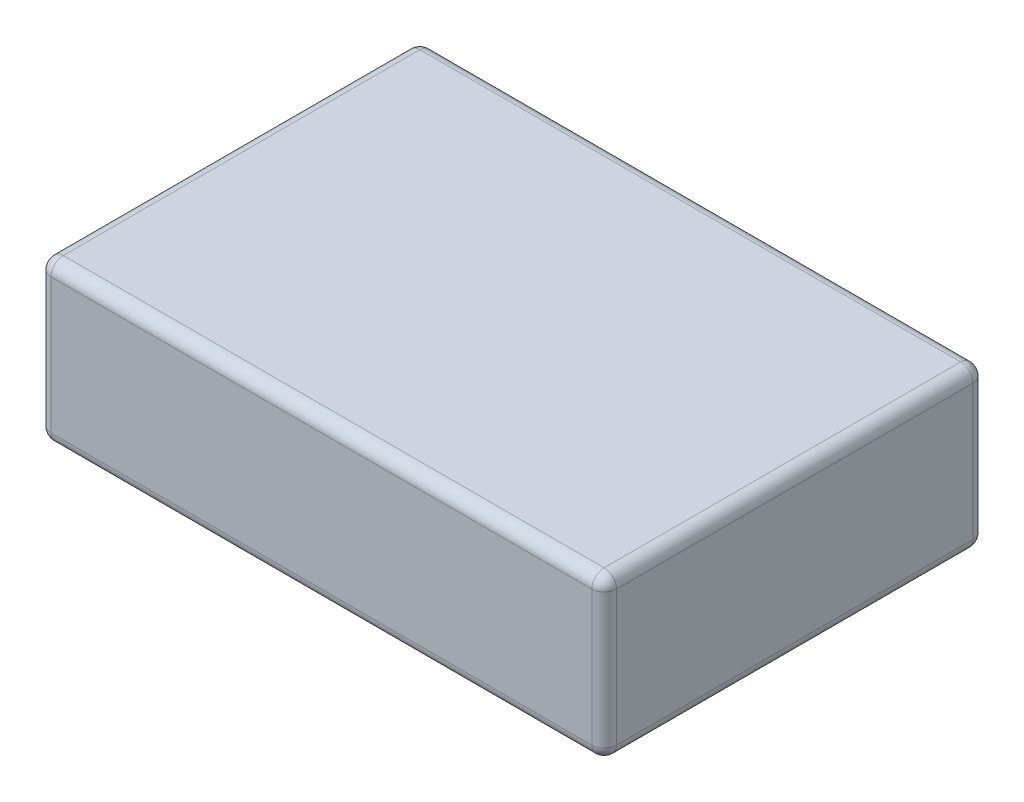
SolidWorks part; units mm, degrees
ref_plane "Plano frontal" through (0, 0, 0) normal (0, 0, 1) x (1, 0, 0)
ref_plane "Plano superior" through (0, 0, 0) normal (0, 1, 0) x (1, 0, 0)
ref_plane "Plano direito" through (0, 0, 0) normal (1, 0, 0) x (0, 0, -1)
sketch "Esboço1" plane through (0, 0, 0) normal (0, 1, 0) x (1, 0, 0)
  line L1 (-46, 31) -> (46, 31)
  line L2 (-46, 31) -> (-46, -31)
  line L3 (-46, -31) -> (46, -31)
  line L4 (46, 31) -> (46, -31)
  line L5 (-46, 31) -> (46, -31) construction
  line L6 (-46, -31) -> (46, 31) construction
  point P0 (0, 0)
  dimension "D1" = 62
  dimension "D2" = 92
extrude "Ressalto-extrusão1" add sketch "Esboço1" along normal blind 26
fillet "Filete1" radius 2 12 edges at (46, 0, 0) (0, 0, -31) (-46, 0, 0) (0, 0, 31) (0, 26, -31) (-46, 26, 0) (0, 26, 31) (46, 13, 31) (-46, 13, 31) (-46, 13, -31) (46, 13, -31) (46, 26, 0)
shell "Casca2" thickness 2
